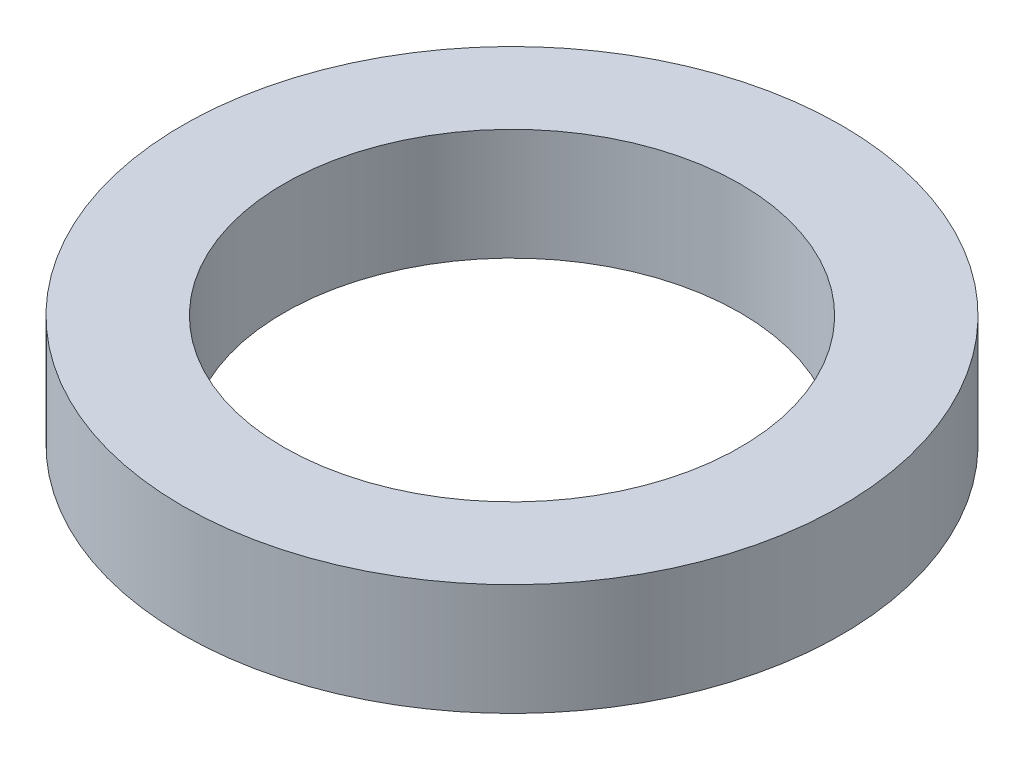
SolidWorks part; units mm, degrees
ref_plane "Front Plane" through (0, 0, 0) normal (0, 0, 1) x (1, 0, 0)
ref_plane "Top Plane" through (0, 0, 0) normal (0, 1, 0) x (1, 0, 0)
ref_plane "Right Plane" through (0, 0, 0) normal (1, 0, 0) x (0, 0, -1)
sketch "Sketch1" plane through (0, 0, 0) normal (0, 1, 0) x (1, 0, 0)
  circle A0 centre (0, 0) radius 6.5
  circle A1 centre (0, 0) radius 4.5
  dimension "D1" = 9
  dimension "D2" = 2
extrude "Boss-Extrude1" add sketch "Sketch1" along normal blind 2.2
